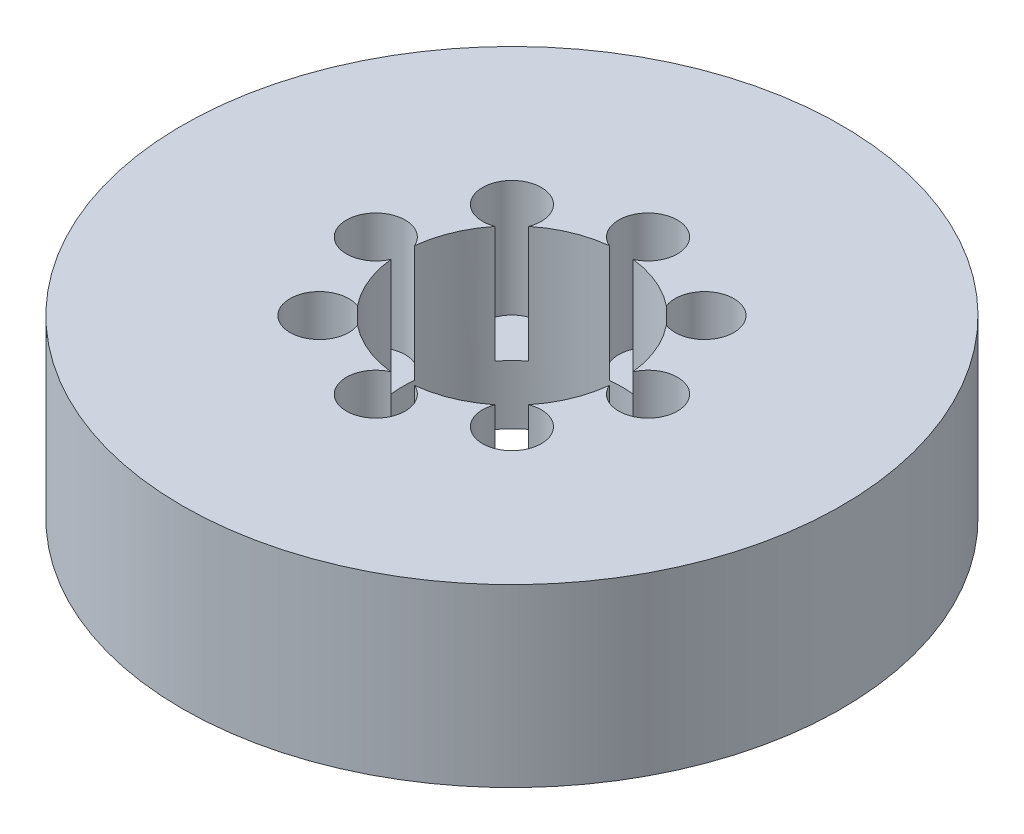
SolidWorks part; units mm, degrees
ref_plane "Front Plane" through (0, 0, 0) normal (0, 0, 1) x (1, 0, 0)
ref_plane "Top Plane" through (0, 0, 0) normal (0, 1, 0) x (1, 0, 0)
ref_plane "Right Plane" through (0, 0, 0) normal (1, 0, 0) x (0, 0, -1)
sketch "Sketch1" plane through (0, 0, 0) normal (0, 1, 0) x (1, 0, 0)
  circle A0 centre (0, 0) radius 52.5
  dimension "FLANGE_OD" = 105
extrude "Boss-Extrude1" add sketch "Sketch1" along normal blind 28
sketch "Sketch2" plane through (0, 0, 0) normal (0, 1, 0) x (1, 0, 0)
  circle A0 centre (0, 0) radius 17.5
  dimension "BORE_D" = 35
extrude "Cut-Extrude1" cut sketch "Sketch2" along normal through all
sketch "Sketch3" plane through (0, 28, 0) normal (0, 1, 0) x (1, 0, 0)
  circle A0 centre (0, 0) radius 21.6845 construction
  circle A1 centre (-21.6845, 0) radius 4.685
  dimension "BOLT_D" = 9.3701
  dimension "BOLT_PCD" = 43.3691
extrude "Cut-Extrude2" cut sketch "Sketch3" against normal blind 18.5791
pattern_circular "CirPattern1" count 8 over 360 about axis through (0, 0, 0) along (0, 1, 0) of "Cut-Extrude2"
